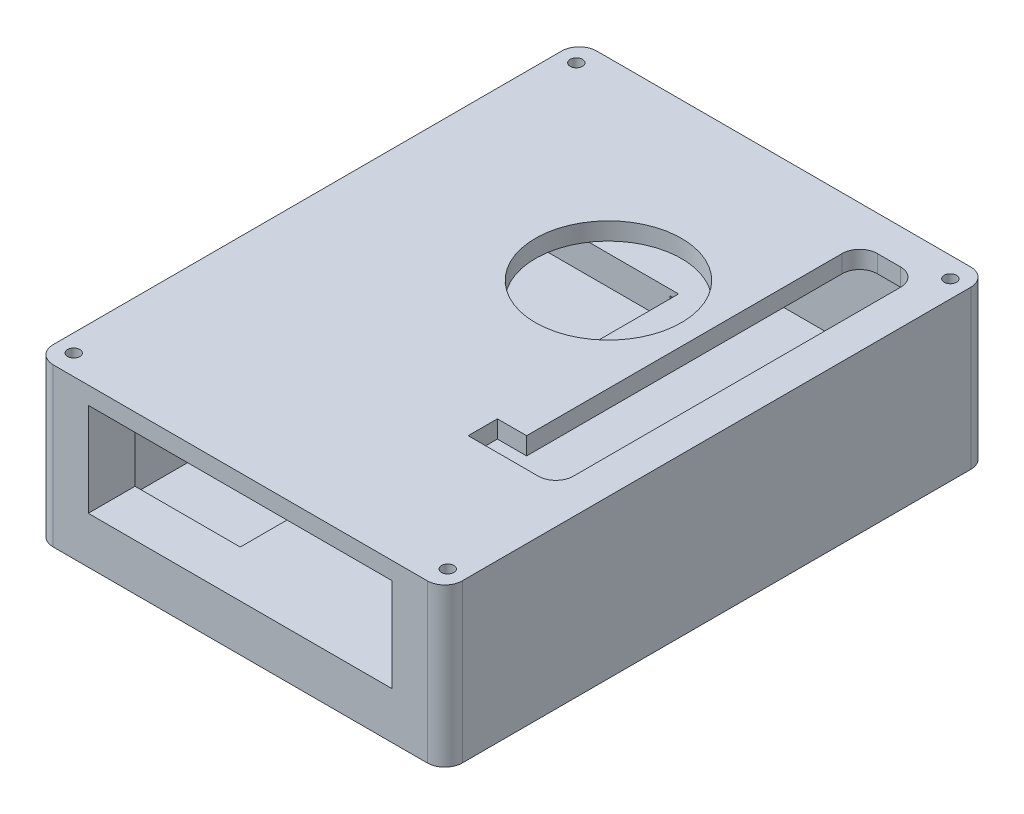
SolidWorks part; units mm, degrees
ref_plane "前视基准面" through (0, 0, 0) normal (0, 0, 1) x (1, 0, 0)
ref_plane "上视基准面" through (0, 0, 0) normal (0, 1, 0) x (1, 0, 0)
ref_plane "右视基准面" through (0, 0, 0) normal (1, 0, 0) x (0, 0, -1)
sketch "草图1" plane through (0, 0, 0) normal (0, 1, 0) x (1, 0, 0)
  line L1 (-32, -46.5) -> (32, -46.5)
  line L2 (-35, -43.5) -> (-35, 43.5)
  line L3 (-32, 46.5) -> (32, 46.5)
  line L4 (35, -43.5) -> (35, 43.5)
  line L5 (-35, -46.5) -> (35, 46.5) construction
  line L6 (-35, 46.5) -> (35, -46.5) construction
  arc A0 (-32, -46.5) -> (-35, -43.5) centre (-32, -43.5) cw
  arc A1 (32, -46.5) -> (35, -43.5) centre (32, -43.5) ccw
  arc A2 (32, 46.5) -> (35, 43.5) centre (32, 43.5) cw
  arc A3 (-35, 43.5) -> (-32, 46.5) centre (-32, 43.5) cw
  point P0 (0, 0)
  dimension "D3" = 3
  dimension "D1" = 93
  dimension "D2" = 70
extrude "凸台-拉伸1" add sketch "草图1" along normal blind 27
sketch "草图2" plane through (-35, 0, 0) normal (-1, 0, 0) x (0, 0, 1)
  line L0 (-43.5, 0) -> (43.5, 0) construction
  line L1 (-36.5, 17) -> (18.5, 17)
  line L2 (-36.5, 17) -> (-36.5, 3)
  line L3 (-36.5, 3) -> (18.5, 3)
  line L4 (18.5, 17) -> (18.5, 3)
  line L5 (-36.5, 17) -> (18.5, 3) construction
  line L6 (-36.5, 3) -> (18.5, 17) construction
  line L7 (-46.5, 27) -> (-46.5, 0) construction
  point P0 (-9, 10)
  dimension "D1" = 55
  dimension "D2" = 14
  dimension "D3" = 3
  dimension "D4" = 10
extrude "切除-拉伸1" cut sketch "草图2" against normal blind 27
sketch "草图3" plane through (0, 0, 46.5) normal (0, 0, 1) x (1, 0, 0)
  line L0 (0, 0) -> (0, 16) construction
  line L1 (-26, 24) -> (26, 24)
  line L2 (-26, 24) -> (-26, 8)
  line L3 (-26, 8) -> (26, 8)
  line L4 (26, 24) -> (26, 8)
  line L5 (-26, 24) -> (26, 8) construction
  line L6 (-26, 8) -> (26, 24) construction
  line L7 (-32, 0) -> (32, 0) construction
  point P0 (0, 16)
  dimension "D1" = 52
  dimension "D2" = 16
  dimension "D3" = 8
extrude "切除-拉伸2" cut sketch "草图3" against normal blind 90
sketch "草图4" plane through (0, 27, 0) normal (0, 1, 0) x (1, 0, 0)
  line L0 (32, 46.5) -> (-32, 46.5) construction
  line L1 (26, 40.5) -> (22, 40.5)
  line L2 (29, 37.5) -> (29, -18.5)
  line L3 (26, -21.5) -> (19, -21.5)
  line L4 (19, 37.5) -> (19, -16.5)
  line L5 (35, -43.5) -> (35, 43.5) construction
  line L7 (19, -21.5) -> (14, -21.5)
  line L9 (19, -16.5) -> (14, -16.5)
  line L10 (14, -21.5) -> (14, -16.5)
  arc A0 (29, -18.5) -> (26, -21.5) centre (26, -18.5) cw
  arc A1 (22, 40.5) -> (19, 37.5) centre (22, 37.5) ccw
  arc A2 (26, 40.5) -> (29, 37.5) centre (26, 37.5) cw
  circle A3 centre (3, 13.5) radius 12.5
  point P10 (29, -21.5)
  point P13 (19, 40.5)
  point P16 (29, 40.5)
  dimension "D5" = 3
  dimension "D8" = 25
  dimension "D1" = 10
  dimension "D2" = 62
  dimension "D3" = 6
  dimension "D4" = 6
  dimension "D6" = 5
  dimension "D7" = 5
  dimension "D9" = 32
  dimension "D10" = 33
extrude "切除-拉伸3" cut sketch "草图4" against normal up to surface (19 mm away) up to face at (-8.5, 8, -3.75)
sketch "草图5" plane through (0, 0, 18.5) normal (0, 0, -1) x (-1, 0, 0)
  line L0 (26, 17) -> (30, 17)
  line L1 (26, 17) -> (35, 17) construction
  line L2 (30, 17) -> (30, 3)
  line L3 (8, 3) -> (35, 3) construction
  line L4 (30, 3) -> (8, 3)
  line L5 (8, 3) -> (8, 8)
  line L6 (8, 8) -> (26, 8)
  line L7 (26, 8) -> (26, 17)
  line L8 (35, 3) -> (35, 17) construction
  dimension "D1" = 5
extrude "切除-拉伸4" cut sketch "草图5" against normal blind 20
sketch "草图6" plane through (0, 27, 0) normal (0, 1, 0) x (1, 0, 0)
  line L0 (32, 43) -> (-32, 43) construction
  line L1 (-32, 43) -> (-32, -43) construction
  line L2 (-32, -43) -> (32, -43) construction
  line L3 (32, -43) -> (32, 43) construction
  line L4 (32, 46.5) -> (-32, 46.5) construction
  line L5 (-32, -46.5) -> (32, -46.5) construction
  line L6 (35, -43.5) -> (35, 43.5) construction
  line L7 (-35, 43.5) -> (-35, -43.5) construction
  circle A0 centre (-32, 43) radius 1.05
  circle A1 centre (-32, -43) radius 1.05
  circle A2 centre (32, -43) radius 1.05
  circle A3 centre (32, 43) radius 1.05
  dimension "D1" = 2.1
  dimension "D2" = 2.1
  dimension "D3" = 2.1
  dimension "D4" = 2.1
  dimension "D5" = 3.5
  dimension "D6" = 3.5
  dimension "D7" = 3
  dimension "D8" = 3
extrude "切除-拉伸5" cut sketch "草图6" against normal through all
sketch "草图7" plane through (0, 0, 0) normal (0, -1, 0) x (1, 0, 0)
  line L0 (32, -46.5) -> (-32, -46.5) construction
  line L1 (11.5, -46.5) -> (-9.5, -46.5)
  line L2 (11.5, -46.5) -> (11.5, -31.5)
  line L3 (8.5, -28.5) -> (-6.5, -28.5)
  line L4 (-9.5, -46.5) -> (-9.5, -31.5)
  line L5 (35, 43.5) -> (35, -43.5) construction
  arc A0 (11.5, -31.5) -> (8.5, -28.5) centre (8.5, -31.5) ccw
  arc A1 (-6.5, -28.5) -> (-9.5, -31.5) centre (-6.5, -31.5) ccw
  dimension "D4" = 3
  dimension "D1" = 21
  dimension "D2" = 23.5
  dimension "D3" = 18
extrude "切除-拉伸6" cut sketch "草图7" against normal blind 7
